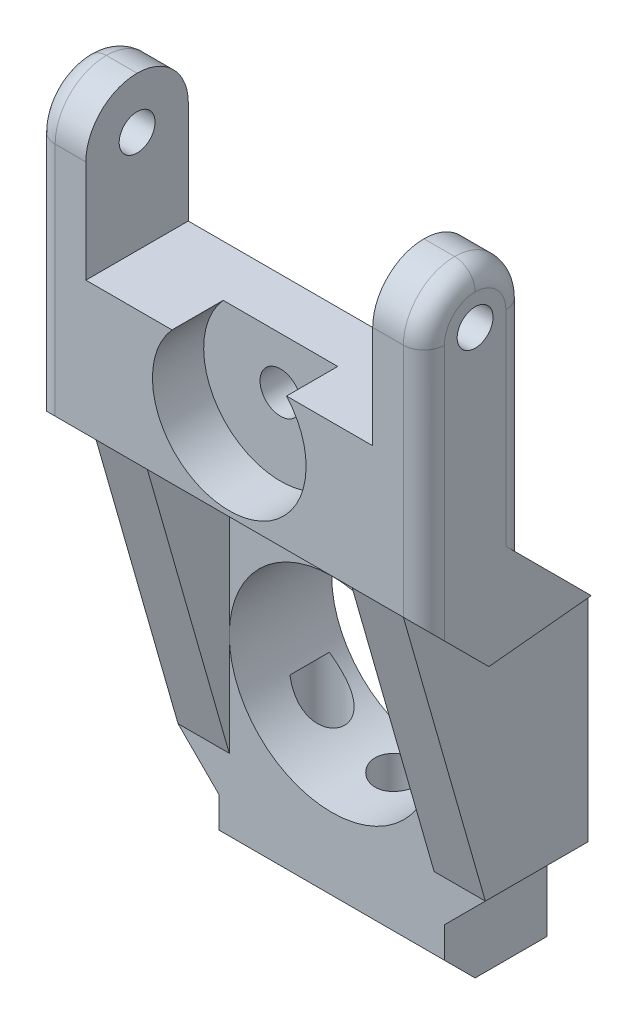
SolidWorks part; units mm, degrees
ref_plane "Front Plane" through (0, 0, 0) normal (0, 0, 1) x (1, 0, 0)
ref_plane "Top Plane" through (0, 0, 0) normal (0, 1, 0) x (1, 0, 0)
ref_plane "Right Plane" through (0, 0, 0) normal (1, 0, 0) x (0, 0, -1)
sketch "Sketch1" plane through (0, 0, 0) normal (0, 0, 1) x (1, 0, 0)
  line L1 (-15, -15.5) -> (15, -15.5)
  line L2 (-15, -15.5) -> (-15, 15.5)
  line L3 (-15, 15.5) -> (15, 15.5)
  line L4 (15, -15.5) -> (15, 15.5)
  line L5 (-15, -15.5) -> (15, 15.5) construction
  line L6 (-15, 15.5) -> (15, -15.5) construction
  point P0 (0, 0)
  dimension "D1" = 30
  dimension "3" = 31
extrude "Boss-Extrude1" add sketch "Sketch1" along normal blind 10
sketch "Sketch2" plane through (0, -15.5, 0) normal (0, -1, 0) x (1, 0, 0)
  line L0 (-15, 0) -> (15, 0) construction
  line L1 (-15, 10) -> (-11, 10)
  line L2 (-15, 10) -> (-15, 0)
  line L3 (-15, 0) -> (-11, 0)
  line L4 (-11, 10) -> (-11, 0)
  line L5 (-15, 10) -> (15, 10) construction
  line L6 (15, 0) -> (11, 0)
  line L7 (15, 0) -> (15, 10)
  line L8 (15, 10) -> (11, 10)
  line L9 (11, 0) -> (11, 10)
  dimension "D1" = 4
extrude "Cut-Extrude1" cut sketch "Sketch2" against normal blind 10
chamfer "Chamfer1" distance 4 angle 45 2 edges at (11, -5.5, 5) (-11, -5.5, 5)
sketch "Sketch3" plane through (0, -15.5, 0) normal (0, -1, 0) x (1, 0, 0)
  line L0 (-7.5, 3.5) -> (7.5, 3.5) construction
  line L1 (0, 3.5) -> (0, 0) construction
  circle A0 centre (-7.5, 3.5) radius 2.25
  circle A1 centre (0, 3.5) radius 2.25
  circle A2 centre (7.5, 3.5) radius 2.25
  dimension "D3" = 4.5
  dimension "D1" = 3.5
  dimension "D2" = 15
extrude "Cut-Extrude2" cut sketch "Sketch3" against normal blind 15
chamfer "Chamfer2" distance 1 angle 45 3 edges at (-7.5, -15.5, 1.25) (0, -15.5, 1.25) (7.5, -15.5, 1.25)
sketch "Sketch4" plane through (0, 0, 0) normal (0, 0, -1) x (-1, 0, 0)
  line L0 (0, 0) -> (0, 4.5) construction
  line L1 (11, -15.5) -> (-11, -15.5) construction
  circle A0 centre (0, 4.5) radius 10
  dimension "D1" = 20
  dimension "D2" = 20
extrude "Cut-Extrude3" cut sketch "Sketch4" against normal through all
sketch "Sketch5" plane through (0, 0, 0) normal (1, 0, 0) x (0, 0, -1)
  line L0 (-10, 14.5) -> (-20, 24.5)
  line L1 (-20, 24.5) -> (-20, 52.5)
  line L2 (-20, 52.5) -> (-10, 52.5)
  line L3 (-10, 52.5) -> (-10, 25.5)
  line L4 (-10, 25.5) -> (0, 15.5)
  line L5 (0, -5.5) -> (0, 15.5) construction
  line L8 (-10, -5.5) -> (-10, 15.5) construction
  line L9 (-10, 14.5) -> (0, 15.5)
  line L10 (-10, 15.5) -> (0, 15.5) construction
  dimension "D1" = 10
  dimension "D2" = 45
  dimension "D3" = 10
  dimension "D4" = 37
  dimension "D5" = 1
extrude "Boss-Extrude2" add sketch "Sketch5" along normal mid plane 38
chamfer "Chamfer3" distance 4 angle 45 2 edges at (-19, 15, 5) (19, 15, 5)
sketch "Sketch6" plane through (0, 52.5, 0) normal (0, 1, 0) x (1, 0, 0)
  line L0 (19, -10) -> (-19, -10) construction
  line L1 (-14, -10) -> (14, -10)
  line L2 (-14, -10) -> (-14, -20)
  line L3 (-14, -20) -> (14, -20)
  line L4 (14, -10) -> (14, -20)
  line L5 (19, -20) -> (-19, -20) construction
  line L6 (0, -10) -> (0, 0) construction
  line L7 (-19, -10) -> (-19, -20) construction
  dimension "D1" = 5
extrude "Cut-Extrude4" cut sketch "Sketch6" against normal blind 15
fillet "Fillet1" radius 5 4 edges at (16.5, 52.5, 10) (16.5, 52.5, 20) (-16.5, 52.5, 10) (-16.5, 52.5, 20)
sketch "Sketch7" plane through (19, 0, 0) normal (1, 0, 0) x (0, 0, -1)
  circle A0 centre (-15, 47.5) radius 1.75
  dimension "D1" = 3.5
extrude "Cut-Extrude5" cut sketch "Sketch7" against normal through all
fillet "Fillet2" radius 2 8 edges at (-19, 36, 20) (-19, 51.0355, 18.5355) (-19, 51.0355, 11.4645) (19, 36, 20) (19, 51.0355, 18.5355) (19, 51.0355, 11.4645) (-19, 36.5, 10) (19, 36.5, 10)
sketch "Sketch8" plane through (0, 0, 20) normal (0, 0, 1) x (1, 0, 0)
  line L0 (0, 32.5) -> (0, 37.5) construction
  line L1 (-14, 37.5) -> (14, 37.5) construction
  circle A0 centre (0, 32.5) radius 2
  dimension "D2" = 4
  dimension "D1" = 5
extrude "Cut-Extrude6" cut sketch "Sketch8" against normal through all
sketch "Sketch9" plane through (0, 0, 20) normal (0, 0, 1) x (1, 0, 0)
  circle A0 centre (0, 32.5) radius 7.5
  dimension "D1" = 15
extrude "Cut-Extrude7" cut sketch "Sketch9" against normal blind 5
sketch "Sketch10" plane through (15, 0, 0) normal (1, 0, 0) x (0, 0, -1)
  line L0 (-10, -5.5) -> (-18, 22.5)
  line L1 (-18, 22.5) -> (-13.6545, 18.1545) construction
  line L2 (-18, 22.5) -> (-10, 14.5)
  line L3 (-10, 14.5) -> (-10, -5.5)
extrude "Boss-Extrude3" add sketch "Sketch10" against normal blind 5
mirror "Mirror1" about plane through (0, 0, 0) normal (1, 0, 0) of "Boss-Extrude3"
chamfer "Chamfer4" distance 3 angle 45 1 edges at (0, -15.5, 10)
